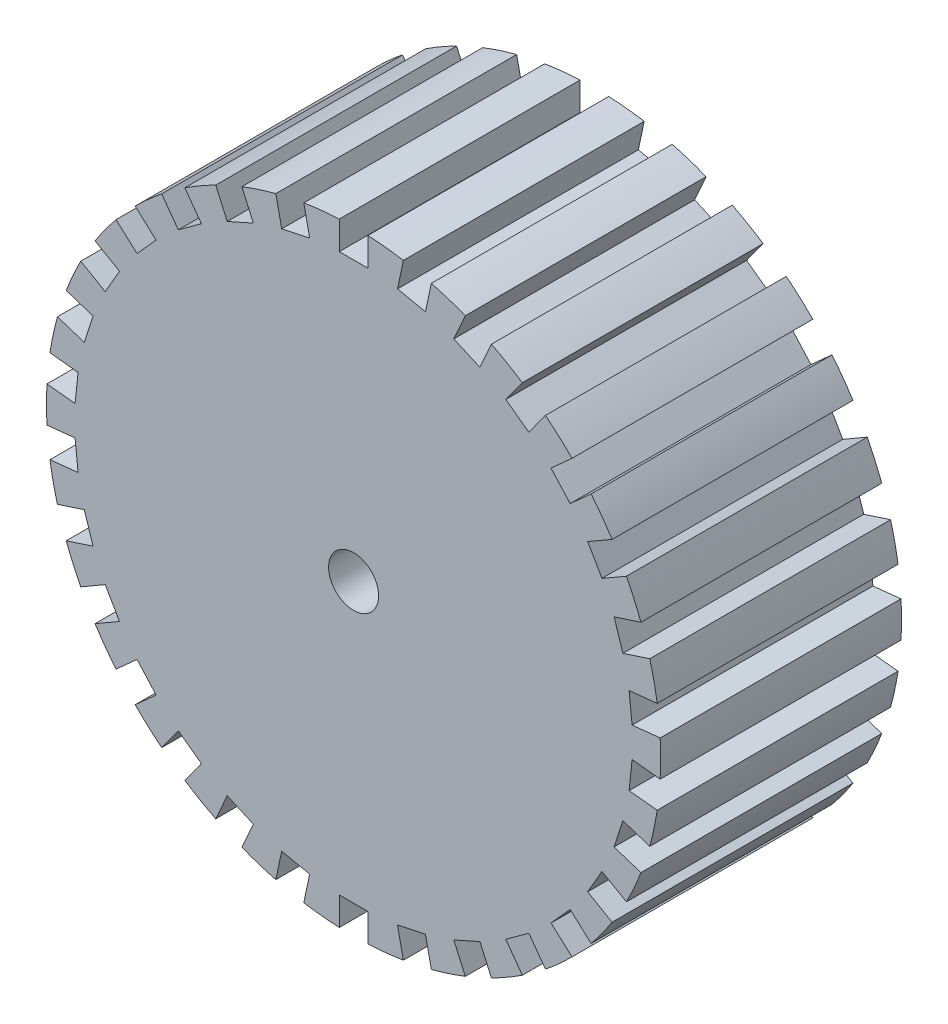
SolidWorks part; units mm, degrees
material "PET"
ref_plane "Alzado" through (0, 0, 0) normal (0, 0, 1) x (1, 0, 0)
ref_plane "Planta" through (0, 0, 0) normal (0, 1, 0) x (1, 0, 0)
ref_plane "Vista lateral" through (0, 0, 0) normal (1, 0, 0) x (0, 0, -1)
sketch "Sketch1" plane through (0, 0, 0) normal (0, 0, 1) x (1, 0, 0)
  circle A0 centre (0, 0) radius 21.5
  circle A1 centre (0, 0) radius 1.75
  dimension "D1" = 43
  dimension "D2" = 3.5
extrude "Boss-Extrude1" add sketch "Sketch1" along normal blind 16.86
sketch "Croquis1" plane through (0, 0, 16.86) normal (0, 0, 1) x (1, 0, 0)
  line L0 (0, 0) -> (0, 21.5) construction
  line L2 (-1, 22.5) -> (1, 22.5)
  line L3 (-1, 22.5) -> (-1, 19.5)
  line L4 (-1, 19.5) -> (1, 19.5)
  line L5 (1, 22.5) -> (1, 19.5)
  circle A0 centre (0, 0) radius 21.5 construction
  point P10 (0, 22.5)
  dimension "D1" = 2
  dimension "D2" = 1
  dimension "D3" = 2
extrude "Cortar-Extruir1" cut sketch "Croquis1" against normal through all
pattern_circular "MatrizC2" count 30 over 360 about axis through (0, 0, 16.86) along (0, 0, -1) of "Cortar-Extruir1"
